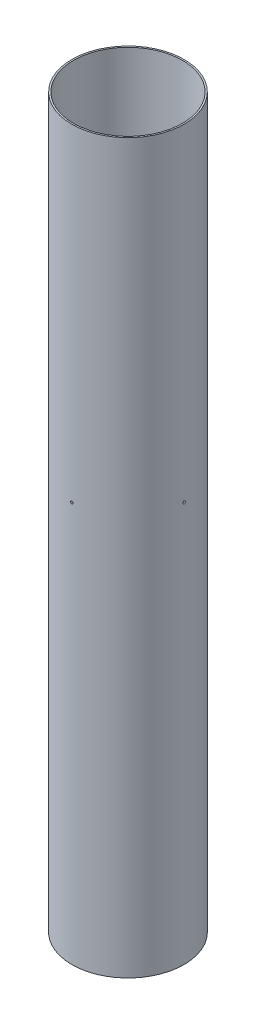
SolidWorks part; units mm, degrees
material "A-Glass Fiber"
ref_plane "Front Plane" through (0, 0, 0) normal (0, 0, 1) x (1, 0, 0)
ref_plane "Top Plane" through (0, 0, 0) normal (0, 1, 0) x (1, 0, 0)
ref_plane "Right Plane" through (0, 0, 0) normal (1, 0, 0) x (0, 0, -1)
sketch "Sketch1" plane through (0, 0, 0) normal (0, 1, 0) x (1, 0, 0)
  circle A0 centre (0, 0) radius 76.1746
  circle A1 centre (0, 0) radius 78.359
  dimension "D1" = 156.718
  dimension "D2" = 152.3492
extrude "Boss-Extrude1" add sketch "Sketch1" along normal blind 1016
ref_axis "Axis1" through (0, 1016, 0) along (0, -1, 0)
sketch "Sketch3" plane through (0, 0, 0) normal (0, 0, 1) x (1, 0, 0)
  line L0 (0, 558.8) -> (0, 1016) construction
  line L1 (78.359, 1016) -> (-78.359, 1016) construction
  circle A0 centre (0, 558.8) radius 1.75
  dimension "D2" = 3.5
  dimension "D1" = 457.2
extrude "Cut-Extrude1" cut sketch "Sketch3" against normal through all
pattern_circular "CirPattern1" count 4 over 360 about axis through (0, 1016, 0) along (0, -1, 0) of "Cut-Extrude1"
equation "\"Fwd_Tube_Length\" = 40in"
equation "\"D1@Boss-Extrude1\" = \"Fwd_Tube_Length\""
equation "\"BKHD_Screw_Diam\"= 3.5mm"
equation "\"Fwd_BKHD_From_Top\" = 18in"
equation "\"D2@Sketch3\"=\"BKHD_Screw_Diam\""
equation "\"D1@Sketch3\"=\"Fwd_BKHD_From_Top\""
equation "\"Bodytube_OD\" = 6.17in"
equation "\"Bodytube_ID\" = 5.998in"
equation "\"D2@Sketch1\"=\"Bodytube_ID\""
equation "\"D1@Sketch1\"=\"Bodytube_OD\""
